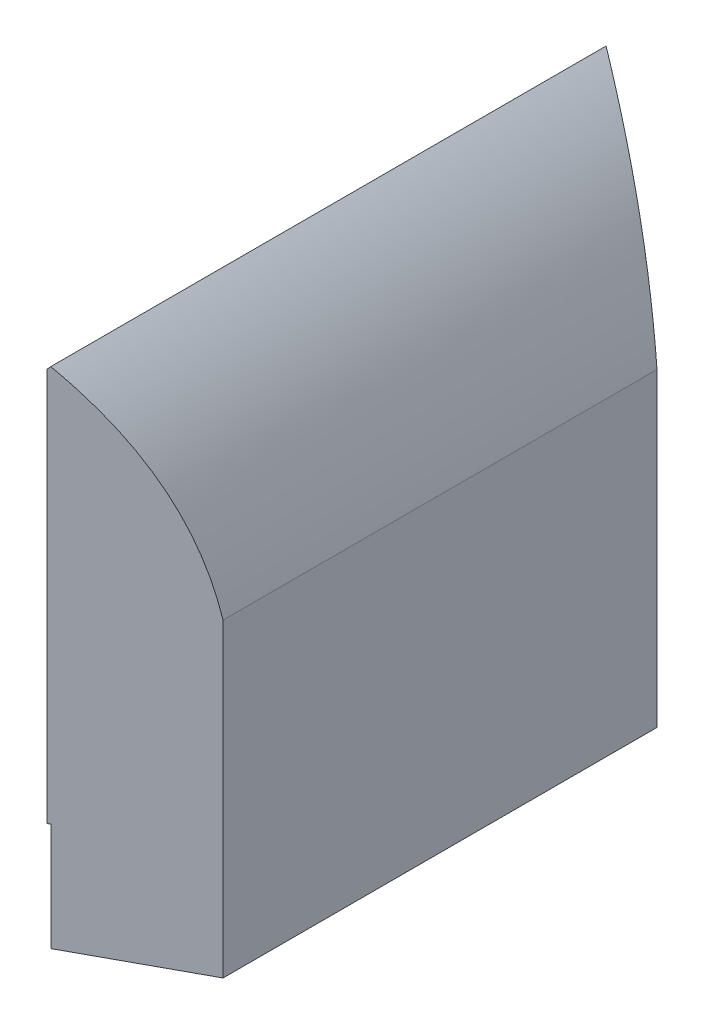
SolidWorks part; units mm, degrees
material "Pine"
ref_plane "Front Plane" through (0, 0, 0) normal (0, 0, 1) x (1, 0, 0)
ref_plane "Top Plane" through (0, 0, 0) normal (0, 1, 0) x (1, 0, 0)
ref_plane "Right Plane" through (0, 0, 0) normal (1, 0, 0) x (0, 0, -1)
sketch "Sketch1" plane through (0, 0, 0) normal (0, 0, 1) x (1, 0, 0)
  line L0 (0, 0) -> (0, -86.95)
  line L1 (0, -86.95) -> (90, -86.95)
  line L2 (90, -86.95) -> (90, 163.05)
  line L3 (3, 0) -> (3, -83.95)
  line L4 (3, -83.95) -> (87, -83.95)
  line L5 (87, -83.95) -> (87, 162.768)
  line L6 (0, 319.5362) -> (-1.9712, 317.2747)
  line L7 (0, 0) -> (3, 0)
  spline S0 degree 2 poles (90, 163.05) (72.3174, 256.4994) (0, 319.5362) knots 0 0 0 1 1 1
  spline S1 degree 1 poles (87, 162.768) (-1.9712, 317.2747) knots 0 0 1 1 construction
  spline S2 degree 3 poles (87, 162.768) (86.6353, 164.6855) (85.8667, 168.5225) (84.1938, 176.0942) (81.8385, 185.4174) (78.5926, 196.3641) (73.7046, 210.6444) (66.5448, 227.9027) (56.2723, 247.6718) (44.3168, 266.5051) (32.9484, 281.4235) (23.0079, 292.8943) (15.1298, 301.2651) (8.2091, 308.0497) (2.4655, 313.3571) (-0.4865, 315.9805) (-1.9712, 317.2747) knots 0.00149 0.00149 0.00149 0.00149 0.032694 0.063897 0.126304 0.188711 0.251118 0.375931 0.500745 0.625559 0.750373 0.812779 0.875186 0.937593 0.968797 1 1 1 1
  dimension "D4" = 184.0681
  dimension "D1" = 86.95
  dimension "D2" = 90
  dimension "D3" = 250
  dimension "D5" = 319.5362
  dimension "D6" = 3
extrude "Boss-Extrude1" add sketch "Sketch1" along normal blind 450
sketch "Sketch2" plane through (0, 0, 0) normal (0, 1, 0) x (1, 0, 0)
  line L0 (-1.9712, -450) -> (90, -400)
  line L1 (90, -450) -> (90, 0) construction
  line L2 (-1.9712, -450) -> (90, -450)
  line L3 (90, -450) -> (90, -400)
  line L4 (0, -225) -> (90, -225) construction
  line L5 (0, -450) -> (0, 0) construction
  line L6 (90, 0) -> (90, -50)
  line L7 (-1.9712, 0) -> (90, 0)
  line L8 (-1.9712, 0) -> (90, -50)
  dimension "D1" = 50
extrude "Cut-Extrude1" cut sketch "Sketch2" against normal through all both and the other way through all contours L6 L8 L7 | L3 L0 L2
sketch "Sketch3" plane through (0, 0, 0) normal (0, 1, 0) x (1, 0, 0)
  line L0 (-1.9712, -446) -> (90, -396)
  line L1 (-1.9712, -450) -> (-1.9712, 0) construction
  line L2 (90, -400) -> (90, -50) construction
  line L3 (-1.9712, -446) -> (-1.9712, -450)
  line L4 (-1.9712, -450) -> (90, -400)
  line L5 (90, -400) -> (90, -396)
  line L6 (90, -225) -> (-1.9712, -225) construction
  line L7 (-1.9712, -4) -> (-1.9712, 0)
  line L8 (90, -50) -> (90, -54)
  line L9 (-1.9712, 0) -> (90, -50)
  line L10 (-1.9712, -4) -> (90, -54)
  dimension "D1" = 4
  dimension "D2" = 4
extrude "Boss-Extrude2" add sketch "Sketch3" along normal up to next and the other way up to next
